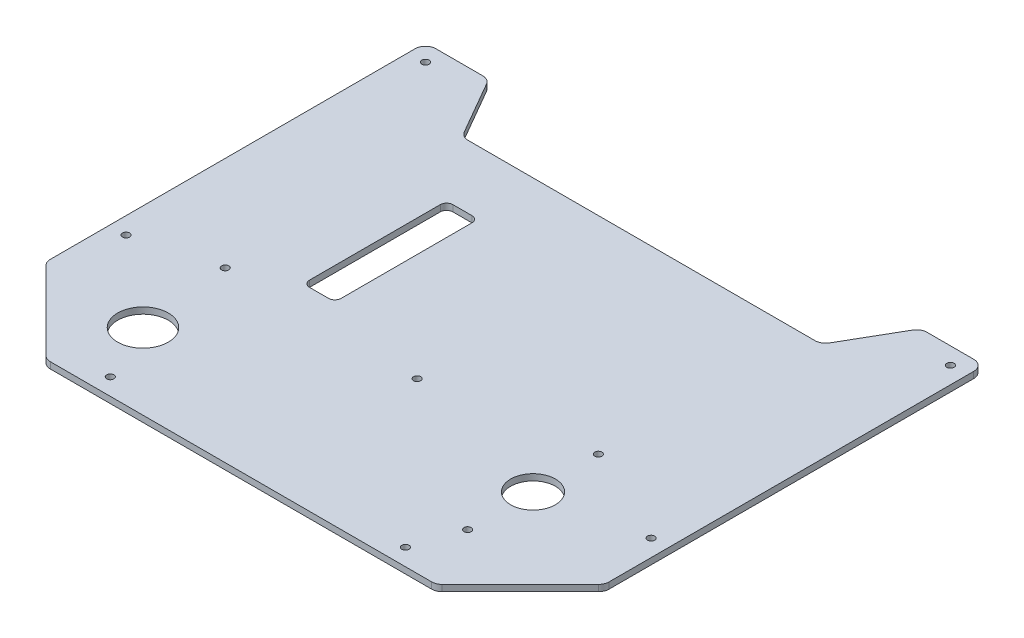
SolidWorks part; units mm, degrees
material "Acier non allié"
ref_plane "Front" through (0, 0, 0) normal (0, 0, 1) x (1, 0, 0)
ref_plane "Top" through (0, 0, 0) normal (0, 1, 0) x (1, 0, 0)
ref_plane "Right" through (0, 0, 0) normal (1, 0, 0) x (0, 0, -1)
sketch "Esquisse1" plane through (0, 0, 0) normal (0, 1, 0) x (1, 0, 0)
  line L0 (0, 0) -> (0, 1919.0564) construction
  line L1 (-92.5, 0) -> (92.5, 0)
  line L2 (92.5, 0) -> (132.5, 40)
  line L3 (132.5, 40) -> (132.5, 220)
  line L4 (132.5, 220) -> (102.5, 220)
  line L5 (102.5, 220) -> (85.1795, 190)
  line L6 (85.1795, 190) -> (-85.1795, 190)
  line L7 (-102.5, 220) -> (-85.1795, 190)
  line L8 (-132.5, 220) -> (-102.5, 220)
  line L9 (-132.5, 40) -> (-132.5, 220)
  line L10 (-92.5, 0) -> (-132.5, 40)
  point P12 (0, 190)
  dimension "D1" = 132.5
  dimension "D2" = 220
  dimension "D3" = 30
  dimension "D4" = 30
  dimension "D5" = 40
  dimension "D6" = 40
  dimension "D7" = 60
extrude "Boss.-Extru.1" add sketch "Esquisse1" along normal blind 3
fillet "Congé1" radius 5 10 edges at (132.5, 1.5, -220) (102.5, 1.5, -220) (85.1795, 1.5, -190) (-85.1795, 1.5, -190) (-102.5, 1.5, -220) (-132.5, 1.5, -220) (-132.5, 1.5, -40) (-92.5, 1.5, 0) (92.5, 1.5, 0) (132.5, 1.5, -40)
sketch "Esquisse2" plane through (0, 0, 0) normal (0, -1, 0) x (1, 0, 0)
  line L0 (0, 0) -> (0, -330.9968) construction
  line L1 (-90.4289, 0) -> (90.4289, 0) construction
  line L2 (-105.3868, -220) -> (-127.5, -220) construction
  line L3 (-132.5, -215) -> (-132.5, -42.0711) construction
  circle A0 centre (-70, -8) radius 1
  circle A1 centre (-124.5, -70) radius 1
  circle A2 centre (-124.5, -212) radius 1
  circle A3 centre (124.5, -212) radius 1
  circle A4 centre (124.5, -70) radius 1
  circle A5 centre (70, -8) radius 1
  dimension "D3" = 2
  dimension "D6" = 2
  dimension "D9" = 2
  dimension "D1" = 70
  dimension "D2" = 8
  dimension "D4" = 124.5
  dimension "D5" = 70
  dimension "D7" = 8
  dimension "D8" = 8
extrude "Enlèv. mat.-Extru.1" cut sketch "Esquisse2" against normal through all
hole_wizard "Dégagement M31" positions "Esquisse3" profile "Esquisse4" hole size "M3" standard "ISO" end condition through all
sketch "Esquisse3" plane through (0, 0, 0) normal (0, -1, 0) x (-1, 0, 0)
  point P0 (-70, 8)
  point P3 (-124.5, 70)
  point P6 (-124.5, 212)
  point P9 (124.5, 212)
  point P12 (124.5, 70)
  point P15 (70, 8)
sketch "Esquisse4" plane through (70, 0, -8) normal (1, 0, 0) x (0, 0, -1)
  line L0 (0, 0) -> (0, 3)
  line L1 (0, 3) -> (1.7, 3)
  line L2 (1.7, 3) -> (1.7, 0)
  line L5 (1.7, 0) -> (0, 0)
  line L11 (0, -6.35) -> (0, 107.95) construction
  dimension "Diamètre du perçage jusqu'au prochain" = 3.4
  dimension "Profondeur du perçage jusqu'au prochain" = 3
sketch "Esquisse5" plane through (0, 0, 0) normal (0, -1, 0) x (1, 0, 0)
  line L6 (132.5, -42.0711) -> (132.5, -215) construction
  line L7 (77.5, -92) -> (77.5, -30) construction
  line L20 (-132.5, -215) -> (-132.5, -42.0711) construction
  line L21 (-90.4289, 0) -> (90.4289, 0) construction
  line L22 (-105.3868, -220) -> (-127.5, -220) construction
  line L23 (-62.5, -160) -> (-47.5, -160)
  line L24 (-62.5, -160) -> (-62.5, -92)
  line L25 (-62.5, -92) -> (-47.5, -92)
  line L26 (-47.5, -160) -> (-47.5, -92)
  line L27 (-87.5, -80) -> (3.5, -80) construction
  circle A0 centre (-82.5, -36) radius 12
  circle A1 centre (-87.5, -80) radius 1.5
  circle A2 centre (3.5, -80) radius 1.5
  circle A3 centre (77.5, -61) radius 10.6
  circle A4 centre (77.5, -92) radius 1.5
  circle A5 centre (77.5, -30) radius 1.5
  point P8 (77.5, -61)
  point P35 (-62.5, -126)
  dimension "D10" = 24
  dimension "D15" = 3
  dimension "D16" = 3
  dimension "D2" = 21.2
  dimension "D6" = 3
  dimension "D7" = 3
  dimension "D3" = 55
  dimension "D4" = 61
  dimension "D5" = 62
  dimension "D8" = 50
  dimension "D9" = 36
  dimension "D11" = 60
  dimension "D12" = 68
  dimension "D13" = 70
  dimension "D14" = 15
  dimension "D17" = 91
  dimension "D18" = 80
  dimension "D19" = 45
extrude "Enlèv. mat.-Extru.2" cut sketch "Esquisse5" against normal through all
fillet "Congé2" radius 3 4 edges at (-62.5, 1.5, -92) (-47.5, 1.5, -92) (-47.5, 1.5, -160) (-62.5, 1.5, -160)
hole_wizard "Dégagement M32" positions "Esquisse6" profile "Esquisse7" hole size "M3" standard "ISO" end condition up to next
sketch "Esquisse6" plane through (0, 3, 0) normal (0, 1, 0) x (1, 0, 0)
  point P0 (-87.5, 80)
  point P3 (3.5, 80)
  point P7 (77.5, 92)
  point P10 (77.5, 30)
sketch "Esquisse7" plane through (-87.5, 3, -80) normal (1, 0, 0) x (0, 0, 1)
  line L0 (0, 0) -> (0, 3)
  line L1 (0, 3) -> (1.7, 3)
  line L2 (1.7, 3) -> (1.7, 0)
  line L5 (1.7, 0) -> (0, 0)
  line L11 (0, -6.35) -> (0, 107.95) construction
  dimension "Diamètre du perçage jusqu'au prochain" = 3.4
  dimension "Profondeur du perçage jusqu'au prochain" = 3
equation "\"WIDTH\"= 300mm'Total width of the robot"
equation "\"LENGTH\"= 220mm'Total length of the robot"
equation "\"CUT_DEPTH\"= 45mm'Depth of the cut on the edges of the plate"
equation "\"Plate_th\"= 3mm'Thickness of the plate"
equation "\"D1\"= \"Plate_th\""
